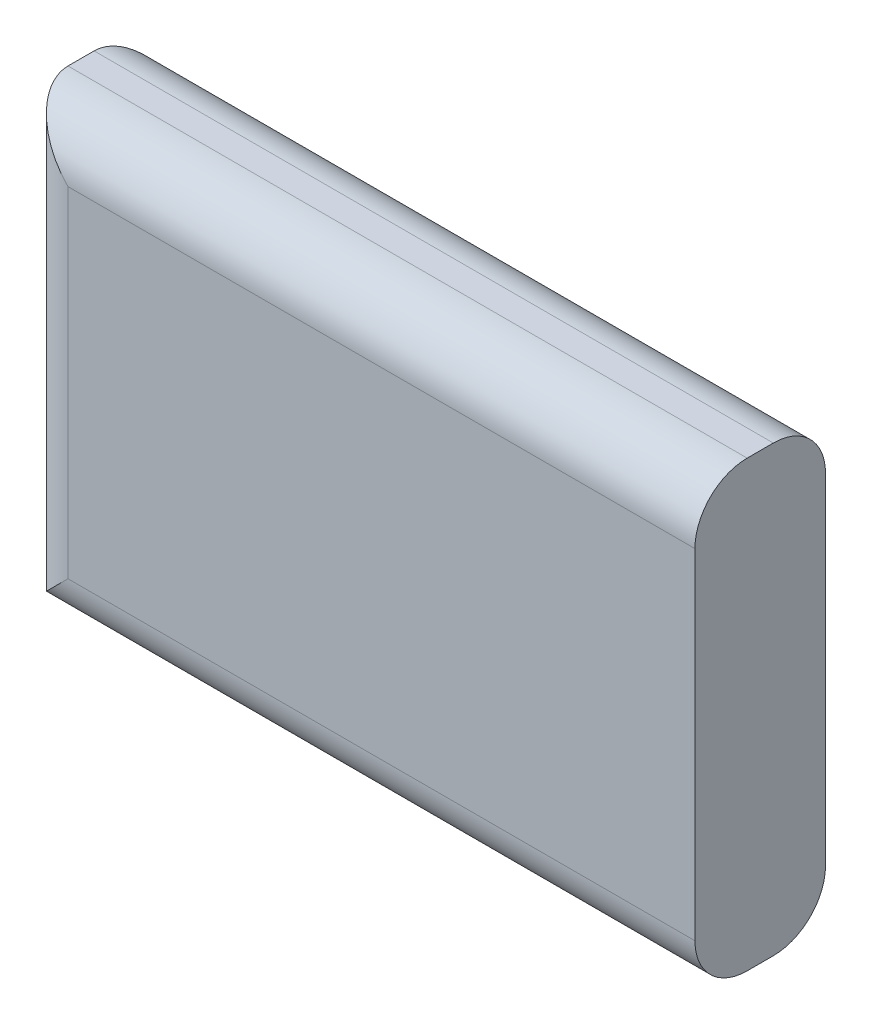
SolidWorks part; units mm, degrees
ref_plane "Front Plane" through (0, 0, 0) normal (0, 0, 1) x (1, 0, 0)
ref_plane "Top Plane" through (0, 0, 0) normal (0, 1, 0) x (1, 0, 0)
ref_plane "Right Plane" through (0, 0, 0) normal (1, 0, 0) x (0, 0, -1)
sketch "Sketch1" plane through (0, 0, 0) normal (0, 0, 1) x (1, 0, 0)
  line L1 (-26, -17) -> (26, -17)
  line L2 (-26, -17) -> (-26, 17)
  line L3 (-26, 17) -> (26, 17)
  line L4 (26, -17) -> (26, 17)
  line L5 (-26, -17) -> (26, 17) construction
  line L6 (-26, 17) -> (26, -17) construction
  point P0 (0, 0)
  dimension "D1" = 52
  dimension "D2" = 34
extrude "Boss-Extrude1" add sketch "Sketch1" along normal mid plane 10
sketch "Sketch2" plane through (0, -17, 0) normal (0, -1, 0) x (1, 0, 0)
  line L5 (-25, -1) -> (-25, 1) construction
  line L7 (-26, 5) -> (-26, -5) construction
  circle A0 centre (-25, 1) radius 0.625
  circle A1 centre (-25, -1) radius 0.625
  point P9 (-26, 0)
  point P10 (-25, 0)
  dimension "D1" = 1.25
  dimension "D2" = 1
  dimension "D3" = 2
extrude "Boss-Extrude2" [suppressed] add sketch "Sketch2" along normal blind 5
fillet "Fillet1" radius 4 6 edges at (-26, 0, 5) (-26, 0, -5) (0, -17, -5) (0, -17, 5) (0, 17, -5) (0, 17, 5)
